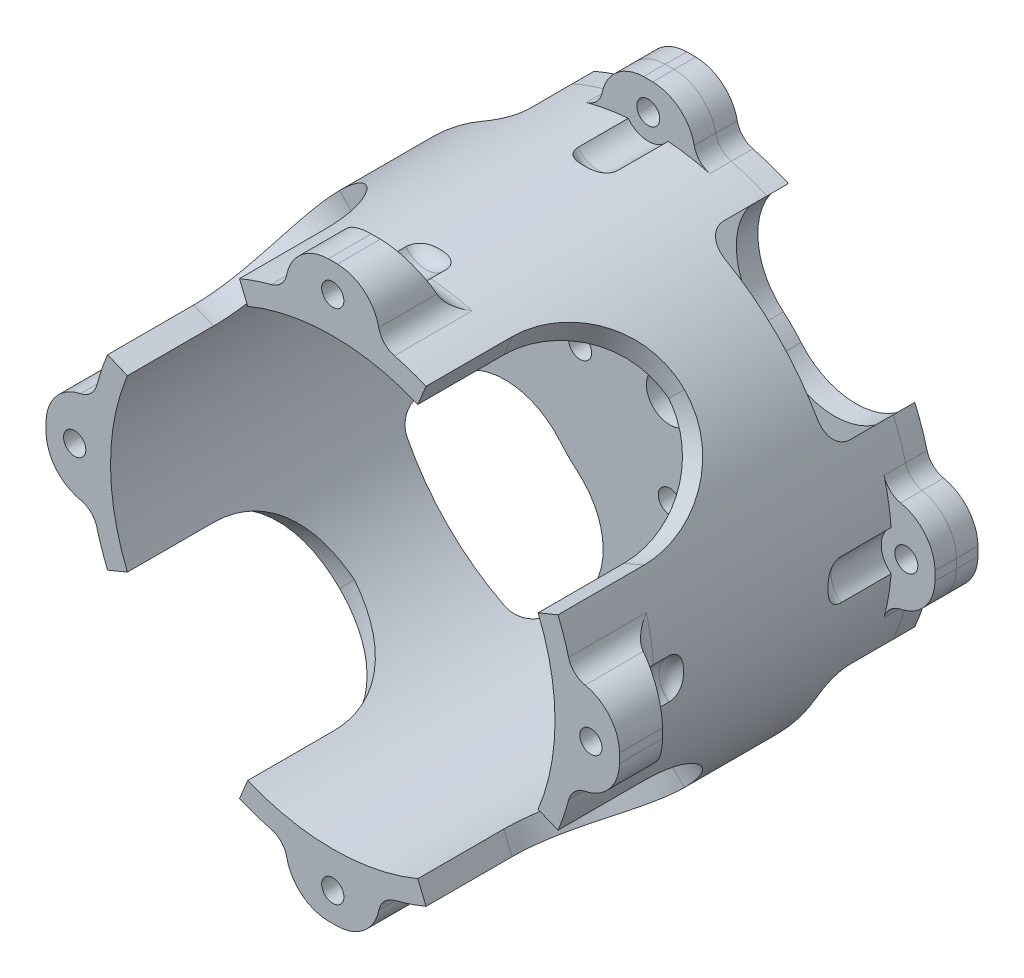
SolidWorks part; units mm, degrees
ref_plane "前视基准面" through (0, 0, 0) normal (0, 0, 1) x (1, 0, 0)
ref_plane "上视基准面" through (0, 0, 0) normal (0, 1, 0) x (1, 0, 0)
ref_plane "右视基准面" through (0, 0, 0) normal (1, 0, 0) x (0, 0, -1)
sketch "草图3" plane through (0, 0, 0) normal (0, 1, 0) x (1, 0, 0)
  line L0 (0, 32.439) -> (0, -17.5) construction
  line L1 (0, 0) -> (34, 0)
  line L2 (34, 0) -> (34, 50)
  line L3 (34, 50) -> (0, 50)
  line L4 (0, 50) -> (0, 0)
  dimension "D1" = 34
  dimension "D2" = 34
  dimension "D3" = 50
revolve "旋转1" add sketch "草图3" angle 360 about L0
shell "抽壳1" thickness 3 removed face at (-34, 0, 0)
sketch "草图5" plane through (0, 0, -50) normal (0, 0, -1) x (-1, 0, 0)
  line L0 (-22.9713, 0) -> (31.9109, 0) construction
  circle A0 centre (0, 0) radius 3.25
  circle A1 centre (0, 0) radius 12.5 construction
  circle A2 centre (12.5, 0) radius 1.6
  circle A3 centre (0, -12.5) radius 1.6
  circle A4 centre (-12.5, 0) radius 1.6
  circle A5 centre (0, 12.5) radius 1.6
  point P17 (0, 0)
  dimension "D1" = 6.5
  dimension "D2" = 25
  dimension "D3" = 3.2
  dimension "D4" = 4
extrude "切除-拉伸4" cut sketch "草图5" against normal up to next
sketch "草图6" plane through (0, 0, -50) normal (0, 0, -1) x (-1, 0, 0)
  line L0 (0, 0) -> (43.0792, 43.0792) construction
  line L1 (0, 0) -> (63.3691, 0) construction
  line L2 (15.3209, 12.8558) -> (0, 0) construction
  line L3 (12.8558, 15.3209) -> (0, 0) construction
  arc A0 (19.2836, 22.9813) -> (22.9813, 19.2836) centre (0, 0) cw construction
  arc A1 (30.6418, 25.7115) -> (25.7115, 30.6418) centre (0, 0) ccw
  arc A2 (15.3209, 12.8558) -> (12.8558, 15.3209) centre (0, 0) ccw
  arc A3 (15.3209, 12.8558) -> (30.6418, 25.7115) centre (22.9813, 19.2836) ccw
  arc A4 (25.7115, 30.6418) -> (12.8558, 15.3209) centre (19.2836, 22.9813) ccw
  arc A5 (12.8558, -15.3209) -> (15.3209, -12.8558) centre (0, 0) ccw
  arc A6 (12.8558, -15.3209) -> (25.7115, -30.6418) centre (19.2836, -22.9813) ccw
  arc A7 (30.6418, -25.7115) -> (15.3209, -12.8558) centre (22.9813, -19.2836) ccw
  arc A8 (25.7115, -30.6418) -> (30.6418, -25.7115) centre (0, 0) ccw
  arc A9 (22.9813, -19.2836) -> (19.2836, -22.9813) centre (0, 0) cw construction
  arc A10 (-15.3209, -12.8558) -> (-12.8558, -15.3209) centre (0, 0) ccw
  arc A11 (-15.3209, -12.8558) -> (-30.6418, -25.7115) centre (-22.9813, -19.2836) ccw
  arc A12 (-25.7115, -30.6418) -> (-12.8558, -15.3209) centre (-19.2836, -22.9813) ccw
  arc A13 (-30.6418, -25.7115) -> (-25.7115, -30.6418) centre (0, 0) ccw
  arc A14 (-19.2836, -22.9813) -> (-22.9813, -19.2836) centre (0, 0) cw construction
  arc A15 (-12.8558, 15.3209) -> (-15.3209, 12.8558) centre (0, 0) ccw
  arc A16 (-12.8558, 15.3209) -> (-25.7115, 30.6418) centre (-19.2836, 22.9813) ccw
  arc A17 (-30.6418, 25.7115) -> (-15.3209, 12.8558) centre (-22.9813, 19.2836) ccw
  arc A18 (-25.7115, 30.6418) -> (-30.6418, 25.7115) centre (0, 0) ccw
  arc A19 (-22.9813, 19.2836) -> (-19.2836, 22.9813) centre (0, 0) cw construction
  point P6 (21.2132, 21.2132)
  point P19 (21.2132, -21.2132)
  point P26 (-21.2132, -21.2132)
  point P33 (-21.2132, 21.2132)
  point P38 (0, 0)
  dimension "D2" = 30
  dimension "D3" = 20
  dimension "D4" = 10
  dimension "D1" = 45
  dimension "D5" = 4
extrude "切除-拉伸5" cut sketch "草图6" against normal blind 12
sketch "草图8" plane through (0, 0, 0) normal (0, 1, 0) x (1, 0, 0)
  line L2 (40, 0) -> (32, 0)
  line L3 (32, 0) -> (32, 10)
  line L4 (0, 50) -> (0, 0) construction
  line L5 (32, 10) -> (40, 6)
  line L6 (40, 6) -> (40, 0)
  line L7 (32, 50) -> (32, 0) construction
  line L8 (-34, 0) -> (34, 0) construction
  line L10 (34, 50) -> (31.1799, 50) construction
  line L11 (0, 25) -> (52.506, 25) construction
  line L12 (13.5579, 50) -> (-13.5579, 50) construction
  dimension "D1" = 6
  dimension "D2" = 8
  dimension "D3" = 10
  dimension "D4" = 32
revolve "旋转2" add sketch "草图8" angle 20 mid plane about L4
sketch "草图9" plane through (0, 0, -50) normal (0, 0, -1) x (-1, 0, 0)
  line L0 (49.1445, 0) -> (-55.9509, 0) construction
  circle A0 centre (-36, 0) radius 3.5
  dimension "D1" = 7
  dimension "D2" = 36
extrude "圆孔位置" cut sketch "草图9" against normal offset from surface (46 mm away) 4
sketch "草图10" plane through (0, 0, -4) normal (0, 0, -1) x (-1, 0, 0)
  circle A0 centre (-36, 0) radius 1.55
  dimension "D1" = 3.1
extrude "1" cut sketch "草图10" against normal up to next
ref_plane "基准面1" through (0, 0, 0) normal (-0.7071, 0.7071, 0) x (0.7071, 0.7071, 0)
sketch "草图13" plane through (0, 0, 0) normal (0, 0, 1) x (1, 0, 0)
  line L0 (0, 0) -> (37.8194, 37.8194) construction
  line L1 (0, 0) -> (73.4797, 0) construction
  line L3 (13.0112, 31.4119) -> (0, 0)
  line L5 (31.4119, 13.0112) -> (0, 0)
  circle A0 centre (0, 0) radius 34 construction
  arc A1 (31.4119, 13.0112) -> (13.0112, 31.4119) centre (0, 0) ccw
  dimension "D1" = 45
  dimension "D2" = 45
extrude "切除-拉伸9" cut sketch "草图13" against normal blind 25
fillet "圆角2" radius 13 2 edges at (30.0261, 12.4372, -25) (12.4372, 30.0261, -25)
fillet "圆角3" radius 3 4 edges at (33.4835, -5.904, -4.5) (33.7204, -4.3512, -9) (33.7204, 4.3512, -9) (33.4835, 5.904, -4.5)
fillet "圆角4" radius 6 2 edges at (39.3923, -6.9459, -3) (39.3923, 6.9459, -3)
fillet "圆角5" radius 3 8 edges at (12.2959, -30.1348, -38) (30.1348, -12.2959, -38) (-12.2959, -30.1348, -38) (-30.1348, -12.2959, -38) (-30.1348, 12.2959, -38) (-12.2959, 30.1348, -38) (12.2959, 30.1348, -38) (30.1348, 12.2959, -38)
pattern_circular "阵列(圆周)2" count 4 over 360 about axis through (0, 0, -50) along (0, 0, -1) of "切除-拉伸9", "1", "旋转2", "圆孔位置", "圆角2", "圆角3", "圆角4"
sketch "草图14" plane through (0, 0, -50) normal (0, 0, -1) x (-1, 0, 0)
  line L0 (0, 0) -> (0, 48.1649) construction
  line L2 (0.6357, 39.9949) -> (-0.6357, 39.9949)
  circle A0 centre (0, 36) radius 1.6
  arc A4 (-2.789, 33.8854) -> (2.789, 33.8854) centre (0, 36) ccw
  arc A5 (-8.5995, 32.8945) -> (-6.4475, 35.0706) centre (-9.3583, 35.797) ccw construction
  arc A6 (-6.4475, 35.0706) -> (-6.419, 35.1965) centre (-9.3583, 35.797) ccw construction
  arc A7 (6.419, 35.1965) -> (6.4475, 35.0706) centre (9.3583, 35.797) ccw construction
  arc A8 (6.419, 35.1965) -> (0.6357, 39.9949) centre (0.5403, 33.9957) ccw construction
  arc A9 (-0.6357, 39.9949) -> (-6.419, 35.1965) centre (-0.5403, 33.9957) ccw construction
  arc A11 (-8.5995, 32.8945) -> (-6.4475, 35.0706) centre (-9.3583, 35.797) ccw
  arc A12 (-6.4475, 35.0706) -> (-6.419, 35.1965) centre (-9.3583, 35.797) ccw
  arc A13 (6.419, 35.1965) -> (6.4475, 35.0706) centre (9.3583, 35.797) ccw
  arc A14 (6.419, 35.1965) -> (0.6357, 39.9949) centre (0.5403, 33.9957) ccw
  arc A15 (-0.6357, 39.9949) -> (-6.419, 35.1965) centre (-0.5403, 33.9957) ccw
  circle A16 centre (0, 36) radius 3.5 construction
  arc A18 (8.5995, 32.8945) -> (2.789, 33.8854) centre (0, 0) ccw
  arc A19 (-2.789, 33.8854) -> (-13.5579, 31.1799) centre (0, 0) ccw construction
  arc A20 (8.5995, 32.8945) -> (6.4475, 35.0706) centre (9.3583, 35.797) cw
  arc A21 (-2.789, 33.8854) -> (-8.5995, 32.8945) centre (0, 0) ccw
  dimension "D1" = 3.2
extrude "凸台-拉伸4" add sketch "草图14" against normal blind 6
pattern_circular "阵列(圆周)3" count 4 over 360 about axis through (0, 0, -32.439) along (0, 0, -1) of "凸台-拉伸4" reverse direction yes
ref_plane "基准面2" through (0, 0, -15) normal (0, 0, 1) x (1, 0, 0)
sketch "草图15" plane through (0, 0, -15) normal (0, 0, 1) x (1, 0, 0)
  circle A0 centre (0, 0) radius 34
  arc A1 (13.5579, 31.1799) -> (8.5995, 32.8945) centre (0, 0) ccw construction
  arc A2 (33.8854, 2.789) -> (33.8854, -2.789) centre (36, 0) ccw construction
  arc A3 (2.789, -33.8854) -> (-2.789, -33.8854) centre (0, -36) ccw construction
  arc A4 (-33.8854, -2.789) -> (-33.8854, 2.789) centre (-36, 0) ccw construction
  arc A5 (-2.789, 33.8854) -> (2.789, 33.8854) centre (0, 36) ccw construction
  arc A6 (33.8854, 2.789) -> (33.8854, -2.789) centre (36, 0) ccw
  arc A7 (2.789, -33.8854) -> (-2.789, -33.8854) centre (0, -36) ccw
  arc A8 (-33.8854, -2.789) -> (-33.8854, 2.789) centre (-36, 0) ccw
  arc A9 (-2.789, 33.8854) -> (2.789, 33.8854) centre (0, 36) ccw
extrude "凸台-拉伸5" add sketch "草图15" against normal blind 20 contours A0 A9 | A0 A6 | A0 A8 | A0 A7 region at (33.3653, 0, -15) region at (0, 33.3653, -15) region at (0, -33.3653, -15) region at (-33.3653, 0, -15)
chamfer "倒角1" [suppressed] distance 2 angle 45
split "分割1" bodies to split 131 127 resulting bodies 128 129 split by face at (0, 0, -47)
fillet "圆角7" radius 2 8 edges at (0, 32.5, -35) (-32.5, 0, -35) (0, -32.5, -35) (0, -32.5, -15) (32.5, 0, -35) (32.5, 0, -15) (0, 32.5, -15) (-32.5, 0, -15)
